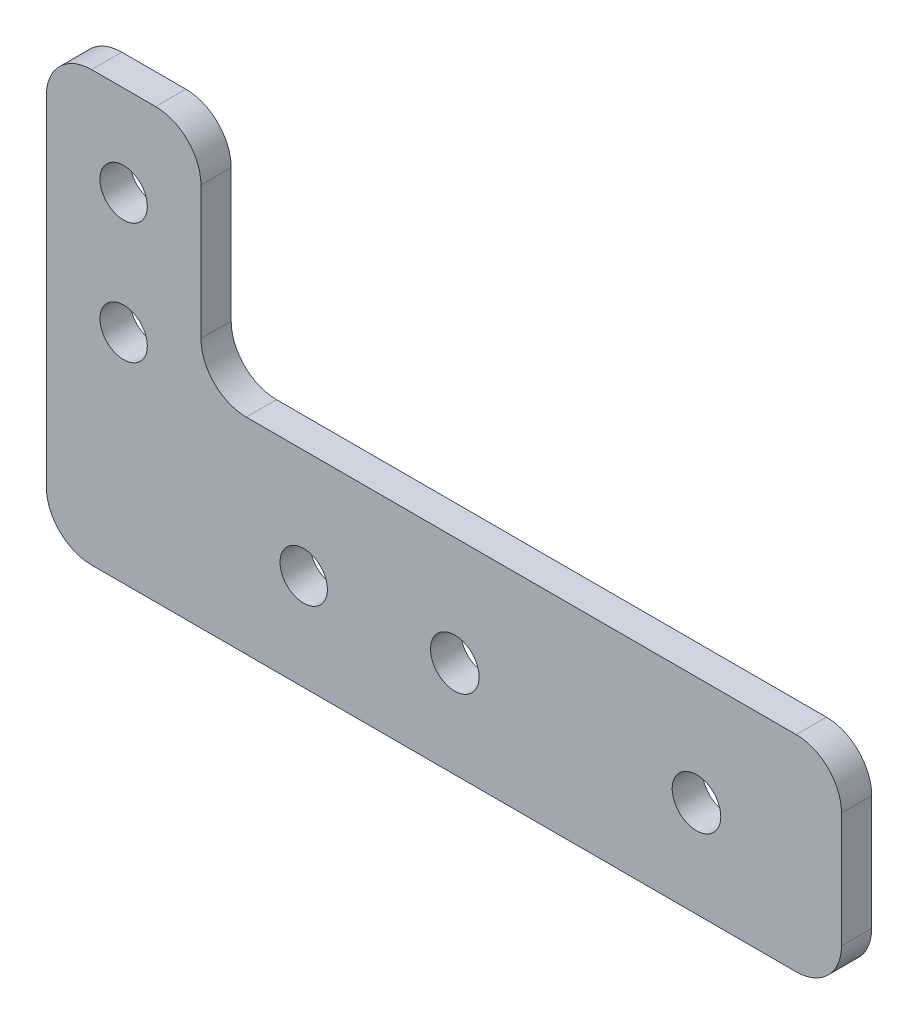
SolidWorks part; units mm, degrees
material "6061-T6 (SS)"
ref_plane "Front Plane" through (0, 0, 0) normal (0, 0, 1) x (1, 0, 0)
ref_plane "Top Plane" through (0, 0, 0) normal (0, 1, 0) x (1, 0, 0)
ref_plane "Right Plane" through (0, 0, 0) normal (1, 0, 0) x (0, 0, -1)
sketch "Sketch1" plane through (0, 0, 0) normal (0, 0, 1) x (1, 0, 0)
  line L0 (-22.86, 23.8125) -> (-39.116, 23.8125) construction
  line L1 (-44.45, -23.8125) -> (44.45, -23.8125)
  line L2 (-44.45, -23.8125) -> (-44.45, 23.8125)
  line L3 (-44.45, 23.8125) -> (44.45, 23.8125)
  line L4 (44.45, -23.8125) -> (44.45, 23.8125)
  line L5 (-44.45, -23.8125) -> (44.45, 23.8125) construction
  line L6 (-44.45, 23.8125) -> (44.45, -23.8125) construction
  line L7 (44.45, 23.8125) -> (-22.86, 23.8125)
  line L8 (44.45, 23.8125) -> (44.45, 0.3175)
  line L9 (44.45, 0.3175) -> (-22.86, 0.3175)
  line L10 (-22.86, 23.8125) -> (-22.86, 0.3175)
  line L11 (-44.45, -23.8125) -> (-39.116, -23.8125)
  line L12 (-44.45, -23.8125) -> (-44.45, 23.8125)
  line L13 (-44.45, 23.8125) -> (-39.116, 23.8125)
  line L14 (-39.116, -23.8125) -> (-39.116, 23.8125)
  line L15 (-39.116, -23.8125) -> (44.45, -23.8125)
  line L16 (-39.116, -23.8125) -> (-39.116, -21.2725)
  line L17 (-39.116, -21.2725) -> (44.45, -21.2725)
  line L18 (44.45, -23.8125) -> (44.45, -21.2725)
  line L19 (-22.86, 23.8125) -> (-39.116, 23.8125) construction
  line L20 (-30.988, 23.8125) -> (-30.988, -21.2725) construction
  circle A0 centre (-30.988, -11.1125) radius 2.4892
  circle A1 centre (-30.988, 1.5875) radius 2.4892
  circle A2 centre (-30.988, 14.2875) radius 2.4892
  circle A4 centre (-12.065, -11.1125) radius 2.4892
  circle A5 centre (3.81, -11.1125) radius 2.5527
  circle A7 centre (29.21, -11.1125) radius 2.5527
  point P0 (0, 0)
  point P31 (0, 0)
  point P32 (0, 0)
  point P33 (0, 0)
  dimension "D7" = 18.923
  dimension "D17" = 44.45
  dimension "D18" = 5.1054
  dimension "D19" = 4.9784
  dimension "D13" = 25.4
  dimension "D1" = 88.9
  dimension "D2" = 9.525
  dimension "D3" = 24.13
  dimension "D4" = 21.59
  dimension "D5" = 5.334
  dimension "D6" = 47.625
  dimension "D9" = 12.7
  dimension "D10" = 12.7
  dimension "D11" = 12.7
  dimension "D12" = 8.128
  dimension "D14" = 27.051
  dimension "D15" = 15.875
  dimension "D16" = 2.54
extrude "Boss-Extrude1" add sketch "Sketch1" along normal blind 3.175 contours L14 L17 L4 L9 L10 L3 A5 A4 A2 A1 A0 | A0 region at (-2.7355, -6.6351, 0) region at (-30.988, -11.1125, 0)
fillet "Fillet1" radius 4.7625 6 edges at (-39.116, 23.8125, 1.5875) (-22.86, 23.8125, 1.5875) (-22.86, 0.3175, 1.5875) (44.45, 0.3175, 1.5875) (44.45, -21.2725, 1.5875) (-39.116, -21.2725, 1.5875)
